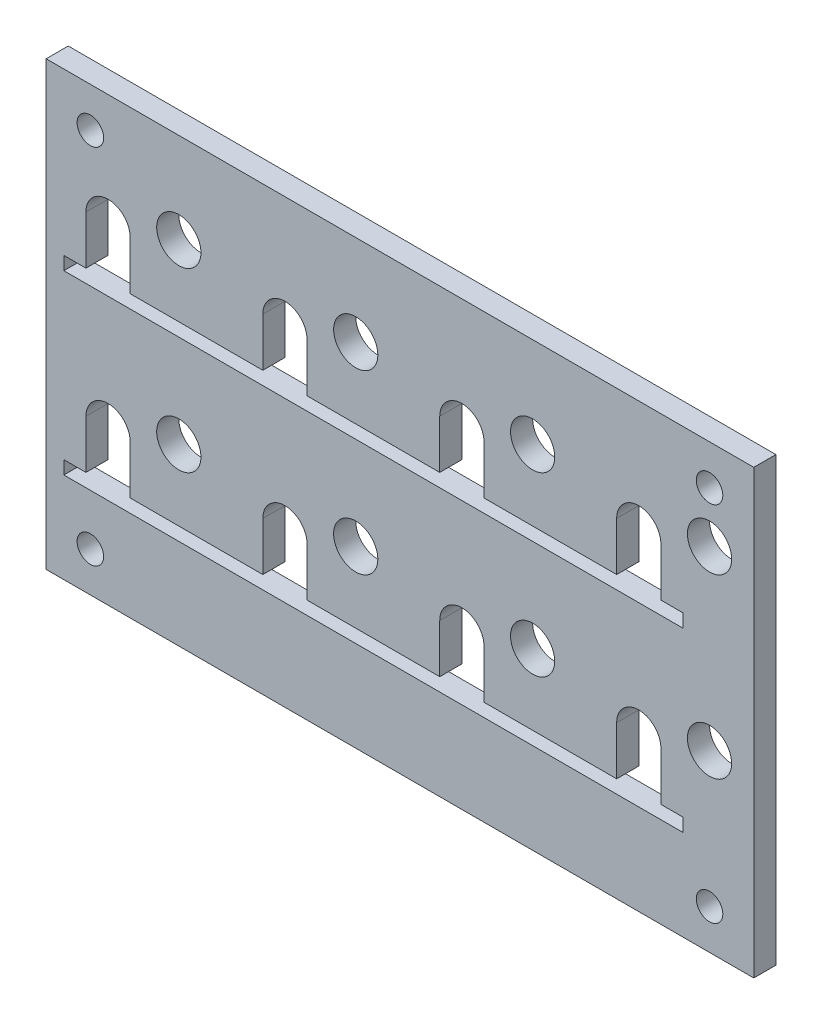
SolidWorks part; units mm, degrees
material "Maple"
ref_plane "Front" through (0, 0, 0) normal (0, 0, 1) x (1, 0, 0)
ref_plane "Top" through (0, 0, 0) normal (0, 1, 0) x (1, 0, 0)
ref_plane "Right" through (0, 0, 0) normal (1, 0, 0) x (0, 0, -1)
sketch "Sketch1" plane through (0, 0, 0) normal (0, 0, 1) x (1, 0, 0)
  line L0 (-10.5, 6.75) -> (-10.5, 14.75)
  line L1 (-40, -25) -> (40, -25)
  line L2 (-40, -25) -> (-40, 25)
  line L3 (-40, 25) -> (40, 25)
  line L4 (40, -25) -> (40, 25)
  line L5 (-40, -25) -> (40, 25) construction
  line L6 (-40, 25) -> (40, -25) construction
  line L7 (-35.5, 6.75) -> (-30.5, 6.75) construction
  line L8 (-35.5, 6.75) -> (-35.5, 14.75)
  line L9 (-35.5, 14.75) -> (-30.5, 14.75)
  line L10 (-30.5, 6.75) -> (-30.5, 14.75)
  line L11 (-35.5, 6.75) -> (-30.5, 14.75) construction
  line L12 (-35.5, 14.75) -> (-30.5, 6.75) construction
  line L13 (-15.5, 14.75) -> (-10.5, 14.75)
  line L14 (-15.5, 6.75) -> (-15.5, 14.75)
  line L15 (9.5, 6.75) -> (9.5, 14.75)
  line L16 (4.5, 14.75) -> (9.5, 14.75)
  line L17 (4.5, 6.75) -> (4.5, 14.75)
  line L18 (29.5, 6.75) -> (29.5, 14.75)
  line L19 (24.5, 14.75) -> (29.5, 14.75)
  line L20 (24.5, 6.75) -> (24.5, 14.75)
  line L21 (-9.061, 0) -> (10.1146, 0) construction
  line L22 (-38, 6.75) -> (-35.5, 6.75)
  line L23 (-30.5, 6.75) -> (-15.5, 6.75)
  line L24 (-10.5, 6.75) -> (4.5, 6.75)
  line L25 (9.5, 6.75) -> (24.5, 6.75)
  line L26 (29.5, 6.75) -> (32, 6.75)
  line L27 (32, 6.75) -> (32, 5.25)
  line L28 (32, 5.25) -> (-38, 5.25)
  line L29 (-38, 5.25) -> (-38, 6.75)
  line L30 (-38, -14.75) -> (-38, -13.25)
  line L31 (-38, -13.25) -> (-35.5, -13.25)
  line L32 (-35.5, -13.25) -> (-35.5, -5.25)
  line L33 (-35.5, -5.25) -> (-30.5, -5.25)
  line L34 (-30.5, -13.25) -> (-30.5, -5.25)
  line L35 (-30.5, -13.25) -> (-15.5, -13.25)
  line L36 (-15.5, -13.25) -> (-15.5, -5.25)
  line L37 (-15.5, -5.25) -> (-10.5, -5.25)
  line L38 (-10.5, -13.25) -> (-10.5, -5.25)
  line L39 (-10.5, -13.25) -> (4.5, -13.25)
  line L40 (4.5, -13.25) -> (4.5, -5.25)
  line L41 (4.5, -5.25) -> (9.5, -5.25)
  line L42 (9.5, -13.25) -> (9.5, -5.25)
  line L43 (9.5, -13.25) -> (24.5, -13.25)
  line L44 (24.5, -13.25) -> (24.5, -5.25)
  line L45 (24.5, -5.25) -> (29.5, -5.25)
  line L46 (29.5, -13.25) -> (29.5, -5.25)
  line L47 (29.5, -13.25) -> (32, -13.25)
  line L48 (32, -13.25) -> (32, -14.75)
  line L49 (32, -14.75) -> (-38, -14.75)
  line L50 (0, -4.8862) -> (0, 4.8862) construction
  circle A0 centre (-25, -5.25) radius 2.5
  circle A1 centre (-5, -5.25) radius 2.5
  circle A2 centre (15, -5.25) radius 2.5
  circle A3 centre (35, -5.25) radius 2.5
  circle A4 centre (35, 20.5) radius 1.5
  circle A5 centre (35, -20.5) radius 1.5
  circle A6 centre (-35, -20.5) radius 1.5
  circle A7 centre (-35, 20.5) radius 1.5
  circle A8 centre (-25, 14.75) radius 2.5
  circle A9 centre (-5, 14.75) radius 2.5
  circle A10 centre (15, 14.75) radius 2.5
  circle A11 centre (35, 14.75) radius 2.5
  point P0 (0, 0)
  point P10 (-33, 10.75)
  point P11 (-13, 14.75)
  point P31 (30.75, 6.75)
  dimension "D14" = 5
  dimension "D18" = 3
  dimension "D1" = 80
  dimension "D2" = 50
  dimension "D3" = 8
  dimension "D4" = 5
  dimension "D6" = 20
  dimension "D7" = 7
  dimension "D8" = 10.25
  dimension "D9" = 70
  dimension "D10" = 1.5
  dimension "D12" = 18.5
  dimension "D13" = 2
  dimension "D16" = 20
  dimension "D17" = 25
  dimension "D19" = 5
  dimension "D20" = 4.5
  dimension "D22" = 20
  dimension "D5" = 4
  dimension "D11" = 2
  dimension "D15" = 4
  dimension "D21" = 2
extrude "Boss-Extrude1" add sketch "Sketch1" along normal blind 2.5 contours L1 L4 L3 L2 L28 L29 L22 L8 L9 L10 L23 L14 L13 L0 L24 L17 L16 L15 L25 L20 L19 L18 L26 L27 L48 L49 L30 L31 L32 L33 L34 L35 L36 L37 L38 L39 L40 L41 L42 L43 L44 L45 L46 L47 region at (0.245, -0.0445, 0)
fillet "Fillet2" radius 2.5 16 edges at (29.5, 14.75, 1.25) (9.5, 14.75, 1.25) (4.5, 14.75, 1.25) (-10.5, 14.75, 1.25) (-15.5, 14.75, 1.25) (-30.5, 14.75, 1.25) (-35.5, 14.75, 1.25) (29.5, -5.25, 1.25) (24.5, -5.25, 1.25) (9.5, -5.25, 1.25) (4.5, -5.25, 1.25) (-10.5, -5.25, 1.25) (-15.5, -5.25, 1.25) (-30.5, -5.25, 1.25) (-35.5, -5.25, 1.25) (24.5, 14.75, 1.25)
